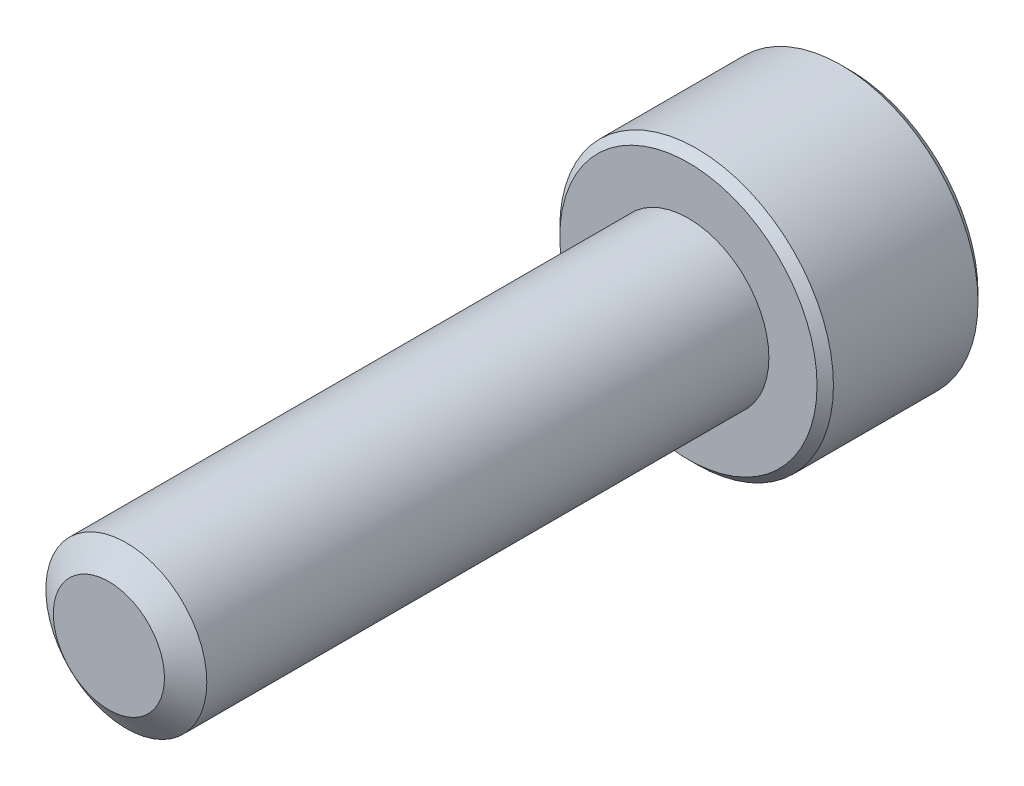
SolidWorks part; units mm, degrees
ref_plane "Front Plane" through (0, 0, 0) normal (0, 0, 1) x (1, 0, 0)
ref_plane "Top Plane" through (0, 0, 0) normal (0, 1, 0) x (1, 0, 0)
ref_plane "Right Plane" through (0, 0, 0) normal (1, 0, 0) x (0, 0, -1)
sketch "Sketch1" plane through (0, 0, 0) normal (0, 0, 1) x (1, 0, 0)
  circle A0 centre (0, 0) radius 2.5
  dimension "OD" = 5
extrude "Extrude1" add sketch "Sketch1" against normal blind 18
sketch "Sketch2" plane through (0, 0, 0) normal (0, 0, 1) x (1, 0, 0)
  circle A0 centre (0, 0) radius 2.5 construction
  circle A1 centre (0, 0) radius 2.5
curve "Helix/Spiral1" pitch 0.8 height 18.8 turns 23.5 parameters "pitch"=0.8
sketch "Sketch3" plane through (0, 0, 0) normal (1, 0, 0) x (0, 0, -1)
  line L0 (-0.7, 2.5) -> (-0.4, 1.9804)
  line L1 (-0.4, 1.9804) -> (-0.3, 1.9804)
  line L2 (-0.3, 1.9804) -> (0, 2.5)
  line L3 (-0.7, 2.5) -> (0, 2.5)
  line L4 (-0.35, 2.5) -> (-0.35, 1.9804) construction
  line L5 (-0.55, 2.2402) -> (-0.15, 2.2402) construction
  line L6 (0, 2.5) -> (0, -2.5) construction
  line L7 (0, -2.5) -> (18, -2.5) construction
  point P11 (3.6, -2.5)
  dimension "D1" = 0.1
  dimension "D2" = 0.4
  dimension "D3" = 60
  dimension "D4" = 3.6
sweep "Cut-Sweep1" [suppressed] cut profiles "Sketch3" path "Helix/Spiral1"
sketch "Sketch4" plane through (0, 0, 0) normal (1, 0, 0) x (0, 0, -1)
  line L0 (0.5417, 2.5) -> (0, 1.7264)
  line L1 (0, 1.7264) -> (0, 2.5)
  line L2 (0.5417, 2.5) -> (0, 2.5)
  line L3 (-0.7, 2.5) -> (0, 2.5) construction
  line L4 (0, 0) -> (7.0209, 0) construction
  dimension "D1" = 55
  dimension "D2" = 0.254
revolve "Cut-Revolve1" cut sketch "Sketch4" angle 360 about L4
sketch "Sketch5" [suppressed] plane through (0, 0, 0) normal (1, 0, 0) x (0, 0, -1)
  line L0 (18, -1.7838) -> (18, 1.991) construction
  line L1 (18, 2.5) -> (0.1203, 2.5)
  line L2 (18, 2.5) -> (18, 0)
  line L3 (18, 0) -> (0.0001, 0)
  line L4 (0.0001, 2.1698) -> (0.0001, 0)
  line L5 (0.1203, 2.5) -> (0.0001, 2.1698)
  line L6 (0, 0) -> (9.9695, 0) construction
  point P3 (0.0001, 2.5)
  point P10 (0.0001, 2.5)
  dimension "D1" = 0.3302
  dimension "Thread min" = 0.0001
  dimension "D3" = 20
revolve "partially thread" [suppressed] add sketch "Sketch5" angle 360 about L6
sketch "Sketch6" plane through (0, 0, -18) normal (0, 0, -1) x (-1, 0, 0)
  circle A0 centre (0, 0) radius 4.25
  dimension "head dia" = 8.5
extrude "Extrude2" add sketch "Sketch6" along normal blind 5
sketch "Sketch7" plane through (0, 0, -23) normal (0, 0, -1) x (-1, 0, 0)
  line L1 (0, 2.3094) -> (-2, 1.1547)
  line L2 (-2, 1.1547) -> (-2, -1.1547)
  line L3 (-2, -1.1547) -> (0, -2.3094)
  line L4 (0, -2.3094) -> (2, -1.1547)
  line L5 (2, -1.1547) -> (2, 1.1547)
  line L6 (2, 1.1547) -> (0, 2.3094)
  circle A0 centre (0, 0) radius 2 construction
  dimension "hex dia" = 4
extrude "Cut-Extrude1" cut sketch "Sketch7" against normal blind 3
sketch "Sketch8" plane through (0, 0, -23) normal (0, 0, -1) x (-1, 0, 0)
  circle A0 centre (0, 0) radius 2.3094
extrude "Cut-Extrude2" cut sketch "Sketch8" against normal through all draft 45
chamfer "Chamfer1" distance 0.255 angle 45 2 edges at (-4.25, 0, -23) (-4.25, 0, -18)
sketch "Sketch9" plane through (0, 0, 0) normal (1, 0, 0) x (0, 0, -1)
  line L0 (0, 2.5) -> (0, -2.5) construction
  line L1 (4.4, 2.5) -> (4.4, -2.5) construction
  dimension "D1" = 4.4
sketch "Sketch10" plane through (0, 0, 0) normal (1, 0, 0) x (0, 0, -1)
  line L0 (18, 2.5) -> (18, 0)
  line L1 (18, 2.5) -> (17.8, 2.5)
  line L2 (17.8, 2.5) -> (16.7645, 0)
  line L3 (18, 0) -> (16.7645, 0)
  line L4 (18, 3.995) -> (18, -3.995) construction
  dimension "D1" = 22.5
  dimension "D2" = 0.2
revolve "Revolve1" add sketch "Sketch10" angle 360 about L3
equation "\"D3@Helix/Spiral1\" = \"screw length@Extrude1\"+\"pitch@Helix/Spiral1\""
equation "\"D1@Sketch3\" = \"pitch@Helix/Spiral1\"*.125"
equation "\"D2@Sketch3\" = \"pitch@Helix/Spiral1\"*.5"
equation "\"D1@Cut-Extrude1\" = \"hex dia@Sketch7\"*.75"
equation "\"D1@Chamfer1\" = \"head dia@Sketch6\"*.03"
equation "\"D1@Sketch9\" = \"pitch@Helix/Spiral1\"*5.5"
equation "\"D2@Sketch10\" = \"pitch@Helix/Spiral1\"*.25"
equation "\"D4@Sketch3\" = \"pitch@Helix/Spiral1\"*4.50"
